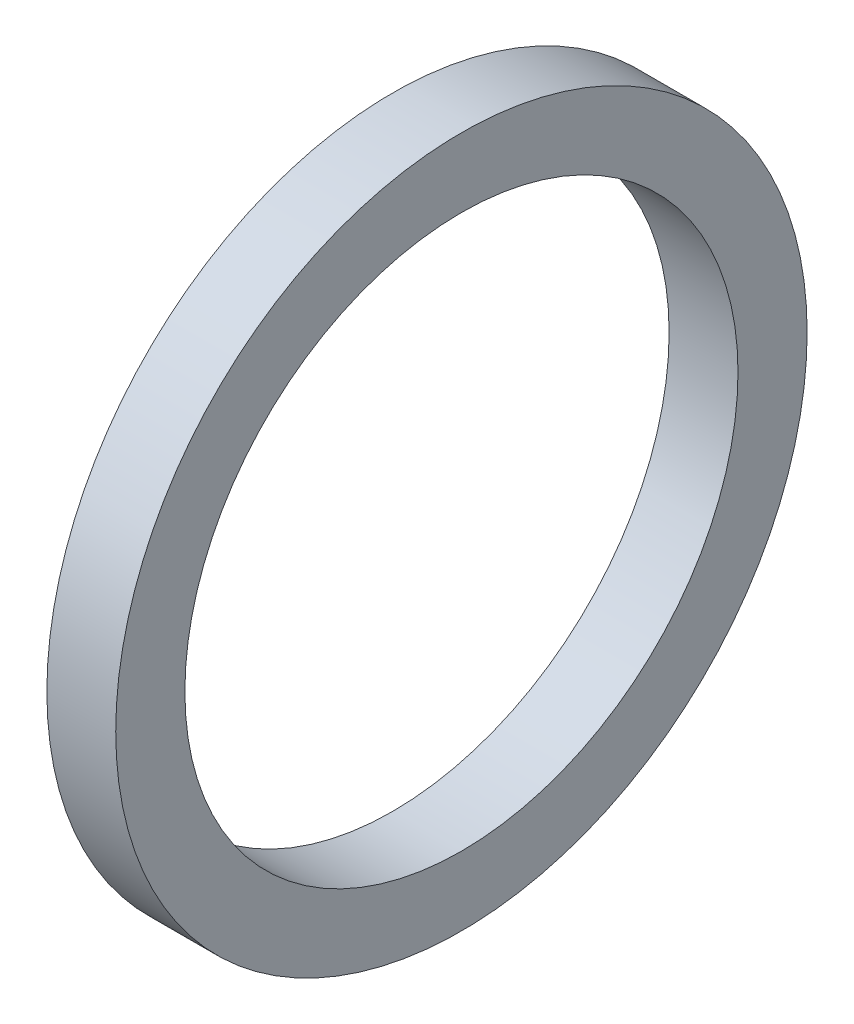
SolidWorks part; units mm, degrees
ref_plane "Front Plane" through (0, 0, 0) normal (0, 0, 1) x (1, 0, 0)
ref_plane "Top Plane" through (0, 0, 0) normal (0, 1, 0) x (1, 0, 0)
ref_plane "Right Plane" through (0, 0, 0) normal (1, 0, 0) x (0, 0, -1)
sketch "Sketch2" plane through (0, 0, 0) normal (0, 0, 1) x (1, 0, 0)
  line L0 (0, 0) -> (58.591, 0) construction
  line L2 (0, 0) -> (18.4, 0)
  line L3 (0, 0) -> (0, 2.5)
  line L4 (0, 2.5) -> (18.4, 2.5)
  line L5 (18.4, 0) -> (18.4, 2.5)
  line L6 (6, 2.5) -> (6, 6)
  line L11 (6, 6) -> (9.97, 6)
  line L16 (12.97, 6) -> (12.97, 3)
  line L17 (12.97, 3) -> (13.6304, 3)
  line L18 (13.6304, 3) -> (13.6304, 2.5)
  line L19 (13.6304, 2.5) -> (6, 2.5)
  line L22 (13.6304, 2.5) -> (16.1104, 2.5)
  line L23 (13.6304, 2.5) -> (13.6304, 4)
  line L24 (13.6304, 4) -> (16.1104, 4)
  line L25 (16.1104, 2.5) -> (16.1104, 4)
  line L27 (6, 6) -> (9.97, 6)
  line L28 (6, 6) -> (6, 9)
  line L29 (6, 9) -> (9.97, 9)
  line L30 (9.97, 6) -> (9.97, 9)
  line L31 (6, 9) -> (6, 8.25)
  line L32 (6, 8.25) -> (5, 8.25)
  line L33 (8.58, 22.001) -> (8.58, 12.476) construction
  line L34 (5, 12.476) -> (12.16, 12.476)
  line L35 (9.97, 9) -> (12.16, 9)
  line L36 (5, 7.5) -> (3, 7.5)
  line L37 (5, 8.25) -> (5, 12.476)
  line L38 (5, 7.5) -> (5, 14)
  line L39 (5, 14) -> (3, 14)
  line L40 (3, 7.5) -> (3, 14)
  line L41 (5, 22.001) -> (12.16, 22.001)
  line L42 (5, 22.001) -> (5, 30.1625)
  line L43 (5, 30.1625) -> (12.16, 30.1625)
  line L44 (12.16, 22.001) -> (12.16, 30.1625)
  line L49 (16.6304, 22.001) -> (16.6304, 7.5)
  line L51 (23.0104, 7.5) -> (23.0104, 6.5)
  line L54 (16.1104, 4) -> (13.6304, 4)
  line L56 (18.0304, 7.5) -> (23.0104, 7.5)
  line L57 (13.16, 22.001) -> (16.6304, 22.001)
  line L58 (16.1104, 3.5) -> (20.0104, 3.5)
  line L59 (29.9004, 14) -> (26.9004, 11)
  line L60 (4, 31.75) -> (18.0304, 31.75)
  line L61 (18.0304, 7.5) -> (23.0104, 7.5)
  line L62 (18.0304, 7.5) -> (18.0304, 12)
  line L63 (18.0304, 12) -> (23.0104, 12)
  line L64 (23.0104, 7.5) -> (23.0104, 12)
  line L65 (18.0304, 31.75) -> (18.0304, 12)
  line L66 (23.0104, 11) -> (26.9004, 11)
  line L67 (34.8004, 23) -> (31.3004, 19.5)
  line L68 (35.8004, 31) -> (38.7904, 33.99)
  line L69 (29.9004, 14) -> (29.9004, 15)
  line L70 (29.9004, 15) -> (22.9304, 15)
  line L71 (22.9304, 15) -> (21.0304, 15)
  line L72 (18.0304, 7.5) -> (16.6304, 7.5)
  line L73 (21.0304, 15) -> (21.0304, 43)
  line L74 (20.0304, 40) -> (10.0704, 40)
  line L75 (10.0704, 40) -> (4, 40)
  line L76 (21.0304, 43) -> (20.0304, 43)
  line L77 (22.9304, 15) -> (29.9004, 15)
  line L78 (22.9304, 15) -> (22.9304, 21)
  line L79 (22.9304, 21) -> (29.9004, 21)
  line L80 (29.9004, 15) -> (29.9004, 21)
  line L81 (10.0704, 40) -> (20.0304, 40)
  line L82 (10.0704, 40) -> (10.0704, 50)
  line L83 (10.0704, 50) -> (20.0304, 50)
  line L84 (20.0304, 40) -> (20.0304, 50)
  line L85 (4, 40) -> (4, 31.75)
  line L86 (12.97, 3) -> (12.97, 2.5)
  line L87 (31.3004, 19.5) -> (29.9004, 19.5)
  line L88 (21.51, 63.5) -> (21.51, 44)
  line L89 (21.51, 63.5) -> (25.9304, 63.5)
  line L90 (25.9304, 63.5) -> (25.9304, 25)
  line L91 (27.8304, 25) -> (25.9304, 25)
  line L92 (10.0704, 48) -> (9, 48)
  line L93 (9, 48) -> (9, 53.476)
  line L94 (9, 53.476) -> (20.0304, 53.476)
  line L95 (20.0304, 53.476) -> (20.0304, 50)
  line L96 (14.5152, 63.001) -> (14.5152, 53.476) construction
  line L97 (9, 63.001) -> (20.0304, 63.001)
  line L98 (9, 63.001) -> (9, 68.2625)
  line L99 (9, 68.2625) -> (20.0304, 68.2625)
  line L100 (20.0304, 63.001) -> (20.0304, 68.2625)
  line L101 (12.97, 6) -> (11.97, 6)
  line L102 (9, 42.5) -> (5, 42.5)
  line L103 (9, 42.5) -> (9, 55)
  line L104 (9, 55) -> (5, 55)
  line L105 (5, 42.5) -> (5, 55)
  line L106 (9.97, 6) -> (10.87, 6)
  line L107 (27.8304, 25) -> (34.8004, 25)
  line L108 (34.8004, 25) -> (34.8004, 23)
  line L109 (0, 0) -> (-2, 0)
  line L110 (0, 0) -> (0, 11)
  line L111 (27.8304, 25) -> (34.8004, 25)
  line L112 (27.8304, 25) -> (27.8304, 32.5)
  line L113 (27.8304, 32.5) -> (34.8004, 32.5)
  line L114 (34.8004, 25) -> (34.8004, 32.5)
  line L115 (35.8004, 31) -> (34.8004, 31)
  line L116 (27.8304, 32.5) -> (27.8304, 64.5)
  line L117 (21.1827, 74.025) -> (6.8477, 74.025)
  line L118 (6.8477, 74.025) -> (6.8477, 76.2)
  line L119 (38.7904, 47.29) -> (30.8304, 55.25)
  line L120 (0, 11) -> (-2, 11)
  line L121 (38.7904, 43.815) -> (30.8529, 43.815)
  line L123 (-4.8, 69.85) -> (1.55, 76.2)
  line L124 (38.7904, 47.29) -> (38.7904, 33.99)
  line L125 (-2, 0) -> (-2, 11)
  line L126 (38.7904, 37.465) -> (30.8529, 37.465)
  line L127 (30.8529, 43.815) -> (30.8529, 37.465)
  line L128 (6, 2.5) -> (6, 0)
  line L129 (0, 63.5) -> (0, 30)
  line L132 (5, 63.5) -> (0, 63.5)
  line L136 (-1.8, 30) -> (-11.76, 30)
  line L138 (-13.76, 25.4) -> (-2, 25.4)
  line L139 (-2, 25.4) -> (-2, 11.5)
  line L140 (27.8304, 64.5) -> (21.1827, 64.5)
  line L141 (-1.8, 30) -> (-11.76, 30)
  line L142 (-1.8, 30) -> (-1.8, 39)
  line L143 (-1.8, 39) -> (-11.76, 39)
  line L144 (-11.76, 30) -> (-11.76, 39)
  line L145 (21.1827, 64.5) -> (21.1827, 74.025)
  line L146 (-12.76, 37) -> (-12.76, 47.29)
  line L147 (-12.76, 37) -> (-11.76, 37)
  line L148 (30.8304, 55.25) -> (30.8304, 76.2)
  line L149 (11.97, 6) -> (11.97, 5.45)
  line L154 (-2, 11.5) -> (1, 11.5)
  line L155 (5, 60.6197) -> (24.05, 60.6197)
  line L160 (5, 60.6197) -> (5, 55.8572)
  line L161 (5, 55.8572) -> (24.05, 55.8572)
  line L166 (24.05, 60.6197) -> (24.05, 55.8572)
  line L167 (5, 60.6197) -> (24.05, 55.8572) construction
  line L172 (5, 55.8572) -> (24.05, 60.6197) construction
  line L173 (24.05, 62.2072) -> (25.9304, 62.2072)
  line L174 (11.97, 5.45) -> (10.87, 5.45)
  line L175 (10.87, 6) -> (10.87, 5.45)
  line L176 (24.05, 62.2072) -> (24.05, 54.2697)
  line L177 (24.05, 54.2697) -> (25.9304, 54.2697)
  line L178 (25.9304, 62.2072) -> (25.9304, 54.2697)
  line L179 (24.05, 62.2072) -> (25.9304, 54.2697) construction
  line L180 (24.05, 54.2697) -> (25.9304, 62.2072) construction
  line L181 (3, 19.6197) -> (15.7, 19.6197)
  line L182 (3, 19.6197) -> (3, 14.8572)
  line L183 (3, 14.8572) -> (15.7, 14.8572)
  line L184 (15.7, 19.6197) -> (15.7, 14.8572)
  line L185 (3, 19.6197) -> (15.7, 14.8572) construction
  line L186 (3, 14.8572) -> (15.7, 19.6197) construction
  line L187 (15.7, 21.2072) -> (16.6304, 21.2072)
  line L188 (15.7, 21.2072) -> (15.7, 13.2697)
  line L189 (15.7, 13.2697) -> (16.6304, 13.2697)
  line L190 (16.6304, 21.2072) -> (16.6304, 13.2697)
  line L191 (15.7, 21.2072) -> (16.6304, 13.2697) construction
  line L192 (15.7, 13.2697) -> (16.6304, 21.2072) construction
  line L193 (1, 11.5) -> (1, 6.5)
  line L194 (1, 6.5) -> (3, 6.5)
  line L195 (23.0104, 6.5) -> (20.0104, 3.5)
  line L196 (5, 63.5) -> (5, 42.5)
  line L197 (5, 42.5) -> (3, 42.5)
  line L198 (3, 42.5) -> (3, 6.5)
  line L199 (6, 0) -> (12.97, 0)
  line L200 (12.97, 0) -> (12.97, 2.5)
  line L201 (18.0304, 31.75) -> (18.0304, 35.875)
  line L202 (18.0304, 35.875) -> (21.0304, 35.875)
  line L203 (30.8304, 76.2) -> (6.8477, 76.2)
  line L204 (3.4027, 69.85) -> (7.8477, 69.85) construction
  line L205 (7.8477, 67.4687) -> (26.8977, 67.4688)
  line L206 (7.8477, 74.025) -> (7.8477, 64.5)
  line L207 (7.8477, 64.5) -> (-1.8, 64.5)
  line L208 (-1.8, 64.5) -> (-1.8, 39)
  line L209 (-12.76, 47.29) -> (-4.8, 55.25)
  line L210 (-4.8, 55.25) -> (-4.8, 69.85)
  line L211 (7.8477, 67.4687) -> (7.8477, 72.2313)
  line L212 (7.8477, 72.2313) -> (26.8977, 72.2313)
  line L213 (26.8977, 67.4688) -> (26.8977, 72.2313)
  line L214 (26.8977, 73.8187) -> (30.8304, 73.8187)
  line L215 (26.8977, 73.8187) -> (26.8977, 65.8813)
  line L216 (26.8977, 65.8813) -> (30.8304, 65.8813)
  line L217 (30.8304, 73.8187) -> (30.8304, 65.8813)
  line L218 (3.4027, 72.2313) -> (25.6277, 72.2313)
  line L219 (3.4027, 72.2313) -> (3.4027, 67.4687)
  line L220 (3.4027, 67.4687) -> (25.6277, 67.4687)
  line L221 (25.6277, 72.2313) -> (25.6277, 67.4687)
  line L222 (25.6277, 69.85) -> (21.1827, 69.85) construction
  line L223 (21.51, 44) -> (22.9304, 44)
  line L224 (22.9304, 44) -> (22.9304, 21)
  line L225 (13.6304, 4) -> (13.6304, 12.2697)
  line L226 (13.6304, 12.2697) -> (13.16, 12.2697)
  line L227 (13.16, 12.2697) -> (13.16, 22.001)
  line L228 (12.16, 9) -> (12.16, 12.476)
  line L229 (-1.8, 30) -> (0, 30)
  line L230 (9, 65.6317) -> (3.4027, 65.6317) construction
  line L231 (20.0304, 65.6317) -> (25.6277, 65.6317) construction
  line L232 (1.55, 76.2) -> (6.8477, 76.2)
  line L233 (-11.76, 30) -> (-13.76, 30)
  line L234 (-13.76, 30) -> (-13.76, 25.4)
  circle A0 centre (26.8804, 25.95) radius 0.95
  circle A1 centre (21.9804, 15.95) radius 0.95
  circle A2 centre (17.3304, 8.2) radius 0.7
  circle A3 centre (10.42, 6.45) radius 0.45
  circle A4 centre (-0.9, 30.9) radius 0.9
  point P7 (24.9902, 58.2385)
  point P131 (16.1652, 17.2385)
  point P135 (14.525, 58.2385)
  point P146 (9.35, 17.2385)
sketch "Sketch3" plane through (0, 0, 0) normal (0, 0, 1) x (1, 0, 0)
  line L0 (20.0304, 40) -> (10.0704, 40) construction
  line L1 (10.0704, 40) -> (10.0704, 50) construction
  line L2 (10.0704, 50) -> (20.0304, 50) construction
  line L3 (20.0304, 40) -> (20.0304, 50) construction
  line L4 (20.0304, 40) -> (10.0704, 40)
  line L5 (10.0704, 40) -> (10.0704, 50)
  line L6 (10.0704, 50) -> (20.0304, 50)
  line L7 (20.0304, 40) -> (20.0304, 50)
revolve "Revolve1" add sketch "Sketch3" angle 360 about L0
